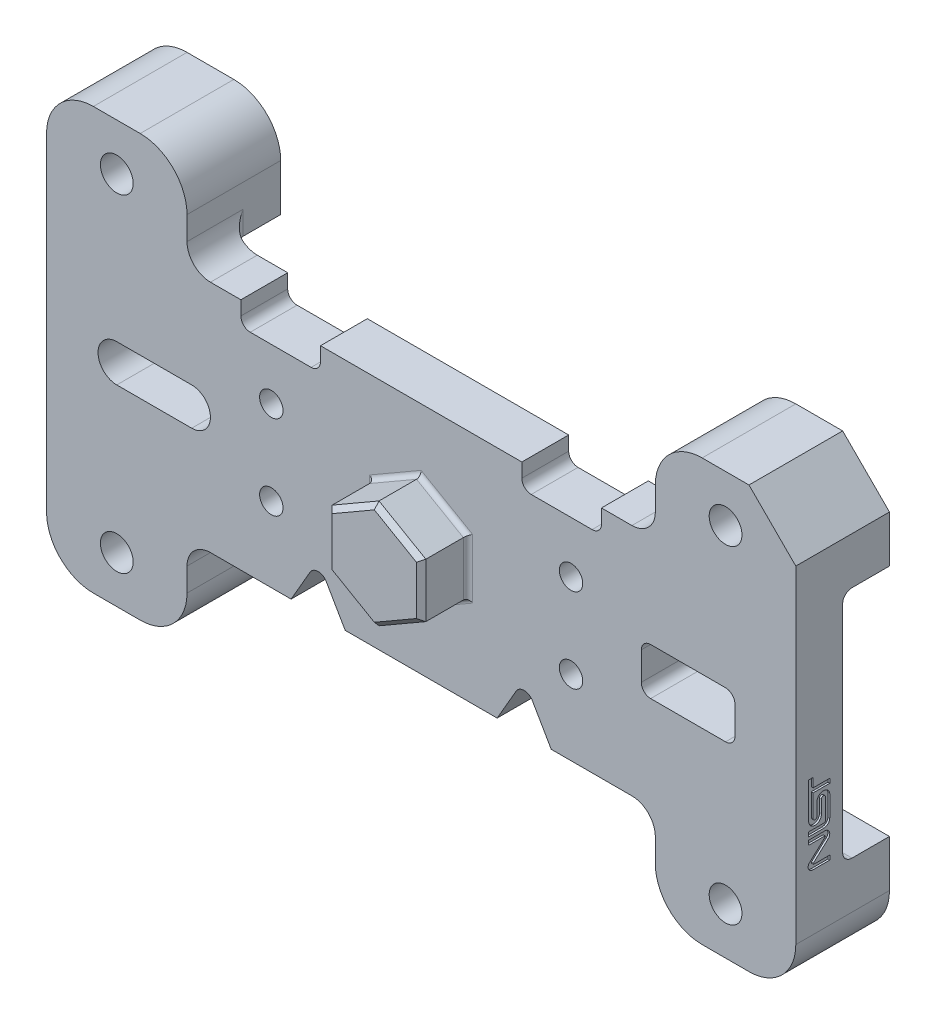
SolidWorks part; units mm, degrees
other "DetailItem8"
other "DetailItem9"
ref_plane "Front Plane" through (0, 0, 0) normal (0, 0, 1) x (1, 0, 0)
ref_plane "Top Plane" through (0, 0, 0) normal (0, 1, 0) x (1, 0, 0)
ref_plane "Right Plane" through (0, 0, 0) normal (1, 0, 0) x (0, 0, -1)
sketch "Sketch1" plane through (0, 0, 0) normal (0, 0, 1) x (1, 0, 0)
  line L0 (300, -225) -> (350, -225)
  line L1 (-350, 225) -> (-300, 225)
  line L2 (-400, 175) -> (-400, -175)
  line L3 (-350, -225) -> (-300, -225)
  line L4 (400, 175) -> (400, -175)
  line L5 (-107.5, 125) -> (107.5, 125)
  line L6 (-250, 175) -> (-250, 150)
  line L7 (-225, 125) -> (-192.5, 125)
  line L8 (250, 175) -> (250, 150)
  line L9 (-225, -125) -> (-138.8675, -125)
  line L10 (-250, -150) -> (-250, -175)
  line L11 (192.5, 125) -> (225, 125)
  line L12 (250, -150) -> (250, -175)
  line L13 (300, 225) -> (350, 225)
  line L14 (-192.5, 125) -> (-192.5, 110)
  line L15 (-182.5, 100) -> (-117.5, 100)
  line L16 (-107.5, 125) -> (-107.5, 110)
  line L17 (0, 0) -> (0, -212.3654) construction
  line L18 (107.5, 125) -> (107.5, 110)
  line L19 (117.5, 100) -> (182.5, 100)
  line L20 (192.5, 125) -> (192.5, 110)
  line L21 (-138.8675, -125) -> (-118.6603, -90)
  line L22 (-101.3397, -90) -> (-81.1325, -125)
  line L23 (-81.1325, -125) -> (81.1325, -125)
  line L24 (81.1325, -125) -> (101.3397, -90)
  line L25 (118.6603, -90) -> (138.8675, -125)
  line L26 (138.8675, -125) -> (225, -125)
  line L27 (350, 225) -> (400, 175)
  line L28 (245, 25) -> (325, 25)
  line L29 (235, 15) -> (235, -15)
  line L30 (245, -25) -> (325, -25)
  line L31 (335, 15) -> (335, -15)
  line L32 (-325, 20) -> (-245, 20)
  line L34 (-325, -20) -> (-245, -20)
  arc A0 (250, 175) -> (300, 225) centre (300, 175) cw
  arc A2 (400, -175) -> (350, -225) centre (350, -175) cw
  arc A3 (300, -225) -> (250, -175) centre (300, -175) cw
  arc A4 (-250, -175) -> (-300, -225) centre (-300, -175) cw
  arc A5 (-350, -225) -> (-400, -175) centre (-350, -175) cw
  arc A6 (-400, 175) -> (-350, 225) centre (-350, 175) cw
  arc A7 (-250, 175) -> (-300, 225) centre (-300, 175) ccw
  arc A8 (-250, -150) -> (-225, -125) centre (-225, -150) cw
  arc A9 (225, -125) -> (250, -150) centre (225, -150) cw
  arc A10 (250, 150) -> (225, 125) centre (225, 150) cw
  arc A11 (-225, 125) -> (-250, 150) centre (-225, 150) cw
  arc A12 (192.5, 110) -> (182.5, 100) centre (182.5, 110) cw
  arc A13 (117.5, 100) -> (107.5, 110) centre (117.5, 110) cw
  arc A14 (-107.5, 110) -> (-117.5, 100) centre (-117.5, 110) cw
  arc A15 (-182.5, 100) -> (-192.5, 110) centre (-182.5, 110) cw
  arc A16 (118.6603, -90) -> (101.3397, -90) centre (110, -95) ccw
  arc A17 (-101.3397, -90) -> (-118.6603, -90) centre (-110, -95) ccw
  arc A18 (325, 25) -> (335, 15) centre (325, 15) cw
  arc A19 (335, -15) -> (325, -25) centre (325, -15) cw
  arc A20 (245, -25) -> (235, -15) centre (245, -15) cw
  arc A21 (235, 15) -> (245, 25) centre (245, 15) cw
  arc A22 (-245, -20) -> (-245, 20) centre (-245, 0) ccw
  arc A23 (-325, -20) -> (-325, 20) centre (-325, 0) cw
  dimension "D8" = 50
  dimension "D13" = 50
  dimension "D19" = 25
  dimension "D20" = 25
  dimension "D21" = 25
  dimension "D22" = 25
  dimension "D24" = 107.5
  dimension "D25" = 107.5
  dimension "D26" = 85
  dimension "D27" = 10
  dimension "D33" = 10
  dimension "D34" = 10
  dimension "D43" = 10
  dimension "D44" = 10
  dimension "D45" = 10
  dimension "D46" = 10
  dimension "D47" = 80
  dimension "D1" = 400
  dimension "D2" = 800
  dimension "D3" = 225
  dimension "D4" = 450
  dimension "D5" = 100
  dimension "D6" = 100
  dimension "D15" = 500
  dimension "D16" = 150
  dimension "D17" = 500
  dimension "D18" = 150
  dimension "D23" = 25
  dimension "D28" = 85
  dimension "D29" = 30
  dimension "D30" = 30
  dimension "D31" = 60
  dimension "D32" = 60
  dimension "D35" = 110
  dimension "D36" = 110
  dimension "D37" = 30
  dimension "D38" = 30
  dimension "D39" = 235
  dimension "D40" = 100
  dimension "D41" = 25
  dimension "D42" = 50
  dimension "D48" = 40
  dimension "D49" = 245
  dimension "D50" = 0
  dimension "D51" = 45
extrude "Boss-Extrude1" add sketch "Sketch1" against normal blind 100
sketch "Sketch2" plane through (0, 0, 0) normal (0, 0, 1) x (1, 0, 0)
  line L1 (0, 57.735) -> (-50, 28.8675)
  line L2 (-50, 28.8675) -> (-50, -28.8675)
  line L3 (-50, -28.8675) -> (0, -57.735)
  line L4 (0, -57.735) -> (50, -28.8675)
  line L5 (50, -28.8675) -> (50, 28.8675)
  line L6 (50, 28.8675) -> (0, 57.735)
  circle A0 centre (0, 0) radius 50 construction
extrude "Boss-Extrude2" add sketch "Sketch2" along normal blind 50
sketch "Sketch3" plane through (0, 0, -100) normal (0, 0, -1) x (-1, 0, 0)
  line L0 (-250, -125) -> (-250, -285.8393)
  line L1 (-250, 257.3417) -> (250, 257.3417)
  line L2 (-250, 257.3417) -> (-250, 125)
  line L3 (-250, -285.8393) -> (250, -285.8393)
  line L4 (250, 257.3417) -> (250, 125)
  line L5 (-508.6386, 125) -> (-250, 125)
  line L6 (-508.6386, 125) -> (-508.6386, -125)
  line L7 (-508.6386, -125) -> (-250, -125)
  line L8 (518.1377, 125) -> (518.1377, -125)
  line L9 (250, -125) -> (250, -285.8393)
  line L10 (250, -125) -> (518.1377, -125)
  line L11 (250, 125) -> (518.1377, 125)
  dimension "D1" = 500
  dimension "D2" = 250
  dimension "D3" = 125
  dimension "D4" = 250
extrude "Cut-Extrude1" cut sketch "Sketch3" against normal blind 50
fillet "Fillet1" radius 10 8 edges at (325, -125, -50) (250, -137.5, -50) (-250, -137.5, -50) (-325, -125, -50) (-250, 137.5, -50) (-325, 125, -50) (250, 137.5, -50) (325, 125, -50)
hole_wizard "Ø20mm Diameter Hole1" positions "Sketch5" profile "Sketch4" hole size "Ø20.0" standard "ISO"
sketch "Sketch5" plane through (0, -125, 0) normal (0, -1, 0) x (-1, 0, 0)
  line L0 (81.1325, 0) -> (-81.1325, 0) construction
  point P0 (30, 25)
  point P2 (-30, 25)
  point P7 (0, 0)
  dimension "D1" = 25
  dimension "D2" = 25
  dimension "D3" = 60
  dimension "D4" = 30
sketch "Sketch4" plane through (-30, -125, -25) normal (1, 0, 0) x (0, 0, -1)
  line L0 (0, 0) -> (0, 51.0086)
  line L1 (0, 51.0086) -> (10, 45)
  line L2 (10, 45) -> (10, 0)
  line L5 (10, 0) -> (0, 0)
  line L10 (0, 51.0086) -> (-10, 45) construction
  line L11 (0, -6.35) -> (0, 107.95) construction
  dimension "Hole Dia." = 20
  dimension "Hole Depth" = 45
  dimension "Drill Angle" = 118
hole_wizard "Ø35mm Diameter Hole1" positions "Sketch7" profile "Sketch6" hole size "Ø0.35" standard "ANSI Metric" end condition through all
sketch "Sketch7" plane through (0, 0, 0) normal (0, 0, 1) x (1, 0, 0)
  point P0 (-325, -175)
  point P2 (-325, 175)
  point P4 (325, 175)
  point P6 (325, -175)
  dimension "D1" = 650
  dimension "D2" = 650
  dimension "D3" = 350
  dimension "D4" = 325
  dimension "D5" = 175
  dimension "D6" = 325
  dimension "D7" = 175
  dimension "D8" = 350
sketch "Sketch6" plane through (-325, -175, 0) normal (1, 0, 0) x (0, -1, 0)
  line L0 (0, 0) -> (0, 100)
  line L1 (0, 100) -> (17.5, 100)
  line L2 (17.5, 100) -> (17.5, 0)
  line L5 (17.5, 0) -> (0, 0)
  line L11 (0, -6.35) -> (0, 107.95) construction
  dimension "Thru Hole Dia." = 35
  dimension "Thru Hole Depth" = 100
hole_wizard "Ø25mm Diameter Hole2" positions "Sketch9" profile "Sketch8" hole size "Ø0.35" standard "ANSI Metric" end condition through all
sketch "Sketch9" plane through (0, 0, 0) normal (0, 0, 1) x (1, 0, 0)
  point P0 (-160, 45)
  point P2 (-160, -45)
  point P4 (160, -45)
  point P6 (160, 45)
  dimension "D1" = 160
  dimension "D2" = 45
  dimension "D3" = 90
  dimension "D4" = 320
  dimension "D5" = 160
  dimension "D6" = 320
  dimension "D7" = 45
  dimension "D8" = 90
sketch "Sketch8" plane through (-160, 45, 0) normal (1, 0, 0) x (0, -1, 0)
  line L0 (0, 0) -> (0, 100)
  line L1 (0, 100) -> (12.5, 100)
  line L2 (12.5, 100) -> (12.5, 0)
  line L5 (12.5, 0) -> (0, 0)
  line L11 (0, -6.35) -> (0, 107.95) construction
  dimension "Thru Hole Dia." = 25
  dimension "Thru Hole Depth" = 100
fillet "Fillet2" radius 5 6 edges at (-25, -43.3013, 0) (-50, 0, 0) (-25, 43.3013, 0) (25, 43.3013, 0) (50, 0, 0) (25, -43.3013, 0)
chamfer "Chamfer1" distance 5 angle 45 6 edges at (50, 0, 50) (25, -43.3013, 50) (-25, -43.3013, 50) (-50, 0, 50) (-25, 43.3013, 50) (25, 43.3013, 50)
ref_point "Point1"
sketch "Sketch13" plane through (400, 0, 0) normal (1, 0, 0) x (0, 0, -1)
  line L0 (13.75, -82.3284) -> (29.9564, -82.3284)
  line L1 (36.25, -76.0347) -> (36.25, -53.234)
  line L2 (22.7156, -53.234) -> (22.7156, -67.6742)
  line L3 (18.4915, -67.5017) -> (18.4915, -43.9666)
  line L4 (18.4915, -43.9666) -> (36.25, -43.9666)
  line L5 (36.25, -43.9666) -> (36.25, -39.3128)
  line L6 (36.25, -39.3128) -> (18.4915, -39.3128)
  line L7 (18.4915, -39.3128) -> (18.4915, -29.6989)
  line L8 (18.4915, -29.6989) -> (13.75, -29.6989)
  line L9 (13.75, -29.6989) -> (13.75, -68.1038)
  line L10 (27.3706, -67.5879) -> (27.3706, -54.0102)
  line L11 (31.5952, -53.9239) -> (31.5952, -75.9911)
  line L12 (29.9564, -77.63) -> (13.75, -77.63)
  line L13 (13.75, -77.63) -> (13.75, -82.3284)
  line L14 (36.25, -115) -> (18.0069, -115)
  line L15 (14.6859, -106.5172) -> (31.3365, -91.1199)
  line L16 (30.8622, -90.0435) -> (13.75, -90.0435)
  line L17 (13.75, -90.0435) -> (13.75, -85.3451)
  line L18 (13.75, -85.3451) -> (30.9743, -85.3451)
  line L19 (34.2709, -94.7398) -> (18.8365, -108.9405)
  line L20 (19.3848, -110.3463) -> (36.25, -110.3463)
  line L21 (36.25, -110.3463) -> (36.25, -115)
  arc A0 (29.9564, -82.3284) -> (36.25, -76.0347) centre (29.9564, -76.0347) ccw
  arc A1 (36.25, -53.234) -> (22.7156, -53.234) centre (29.4828, -54.3117) ccw
  arc A2 (18.4915, -67.5017) -> (22.7156, -67.6742) centre (20.6, -67.6742) ccw
  arc A3 (13.75, -68.1038) -> (27.3706, -67.5879) centre (20.5701, -68.1038) ccw
  arc A4 (31.5952, -53.9239) -> (27.3706, -54.0102) centre (29.4876, -54.1942) ccw
  arc A5 (14.6859, -106.5172) -> (18.0069, -115) centre (18.0069, -110.1085) ccw
  arc A6 (31.3365, -91.1199) -> (30.8622, -90.0435) centre (30.9143, -90.6633) ccw
  arc A7 (18.8365, -108.9405) -> (19.3848, -110.3463) centre (19.3848, -109.5365) ccw
  arc A8 (29.9564, -77.63) -> (31.5952, -75.9911) centre (29.9564, -75.9911) ccw
  arc A9 (34.2709, -94.7398) -> (30.9743, -85.3451) centre (30.9743, -90.6208) ccw
extrude "Cut-Extrude2" cut sketch "Sketch13" against normal blind 2
